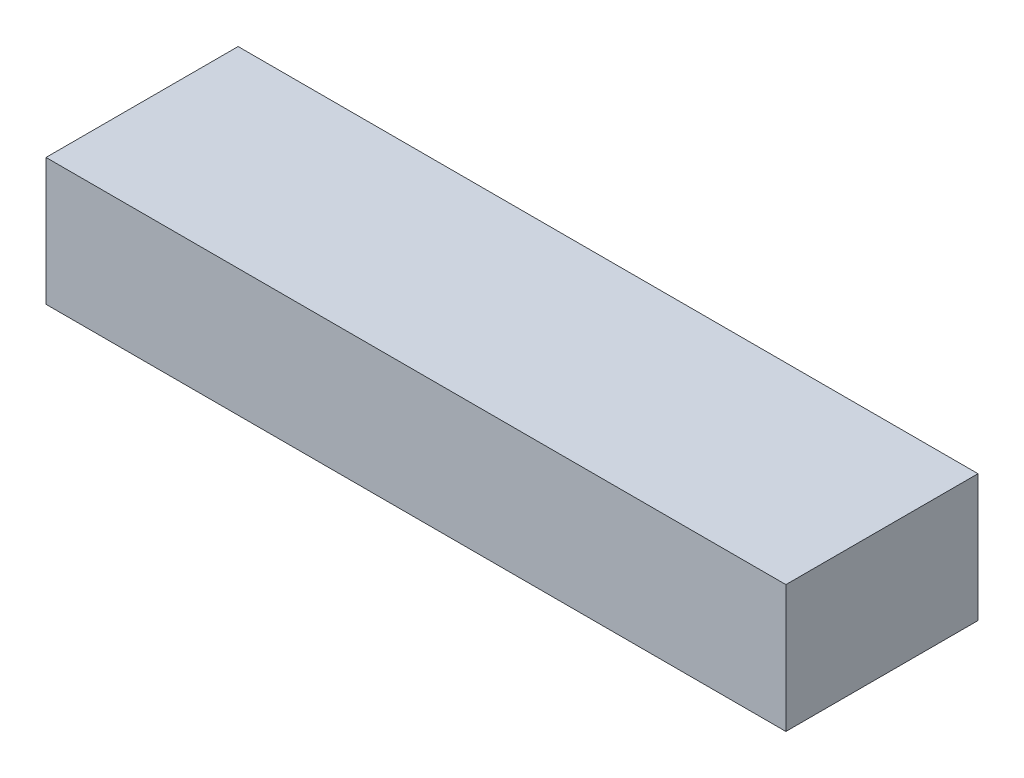
SolidWorks part; units mm, degrees
ref_plane "Front Plane" through (0, 0, 0) normal (0, 0, 1) x (1, 0, 0)
ref_plane "Top Plane" through (0, 0, 0) normal (0, 1, 0) x (1, 0, 0)
ref_plane "Right Plane" through (0, 0, 0) normal (1, 0, 0) x (0, 0, -1)
sketch "Sketch1" plane through (0, 0, 0) normal (0, 1, 0) x (1, 0, 0)
  line L1 (570, -148) -> (-570, -148)
  line L2 (570, -148) -> (570, 148)
  line L3 (570, 148) -> (-570, 148)
  line L4 (-570, -148) -> (-570, 148)
  line L5 (570, -148) -> (-570, 148) construction
  line L6 (570, 148) -> (-570, -148) construction
  point P0 (0, 0)
  dimension "D1" = 1140
  dimension "D2" = 296
extrude "Boss-Extrude1" add sketch "Sketch1" along normal blind 196
equation "\"thickness 1\"= 2"
equation "\"thickness 2\"= 3"
equation "\"connecting flange\"= 35"
equation "\"main length\"= 1200"
equation "\"main width\"= 1200"
equation "\"divider panel distance offset\"= 296"
equation "\"access hatch length\"= \"access hatch cutout length\" + \"access hatch offset\" * 2"
equation "\"access hatch width\"= \"access hatch cutout width\" + \"access hatch offset\" * 2"
equation "\"side panel length\"= 1200"
equation "\"side panel width\"= 950"
equation "\"drift eliminator size offset\"= 10"
equation "\"drift eliminator depth\"= \"divider panel distance offset\""
equation "\"D2@Sketch1\"=\"drift eliminator depth\""
equation "\"thickness radius 1\"= 3.7366"
equation "\"connecting flange holes\"= 8"
equation "\"connecting flange hole gap\"= 100"
equation "\"cut out flange\"= 15 "
equation "\"top panel slot length\"= 250"
equation "\"top panel slot width\"= 700"
equation "\"access hatch cutout length\"= 400"
equation "\"access hatch cutout width\"= 600"
equation "\"access hatch cutout offset X\"= 100"
equation "\"access hatch cutout offset Y\"= 100"
equation "\"slotted panel length\"= \"main length\" + 100"
equation "\"slotted panel width\"= \"main width\""
equation "\"slot count x\"= 3"
equation "\"slot count y\"= 11"
equation "\"slot offset\"= \"water tray depth\""
equation "\"slot length\"= 30"
equation "\"slot width\"= 200"
equation "\"slot offset x\"= \"slot length\" + \"slot offset\""
equation "\"slot offset y\"= \"slot width\" + \"slot offset\""
equation "\"guide rail flange\"= 40"
equation "\"guid rail flange mount side\"= 20"
equation "\"guid rail back length\"= \"main width\" - \"guide rail flange\" * 2"
equation "\"splash plate length\"= 400"
equation "\"splash plate width\"= \"main width\""
equation "\"splash plate air gap\"= 200"
equation "\"splash plate slot count\"= 11"
equation "\"splash plate slot length\"= 50"
equation "\"splash plate slot height\"= 50"
equation "\"splash plate slot offset\"= 65"
equation "\"water tray depth\"= 150"
equation "\"water tray width\"= 200"
equation "\"water tray panel length\"= 473"
equation "\"dimpled panel length\"= \"main length\" - 200 - \"water tray depth\"/2"
equation "\"dimpled panel top offset\"= \"water tray depth\"/2"
equation "\"dimpled panel width\"= \"main width\""
equation "\"dimple panel slot count\"= 119"
equation "\"dimple panel slot length\"= 10"
equation "\"dimple panel slot width\"= 5"
equation "\"dimple panel slot offset\"= 10"
equation "\"sump base flat section width\"= 300"
equation "\"sump upper depth\"= 300"
equation "\"sump depth\"= 550"
equation "\"leg length\"= \"sump depth\" + 150"
equation "\"leg width\"= 80"
equation "\"leg depth\"= 40"
equation "\"leg support plate size\"= \"leg width\" - \"thickness 2\" * 2"
equation "\"leg base plate thickness\"= 8"
